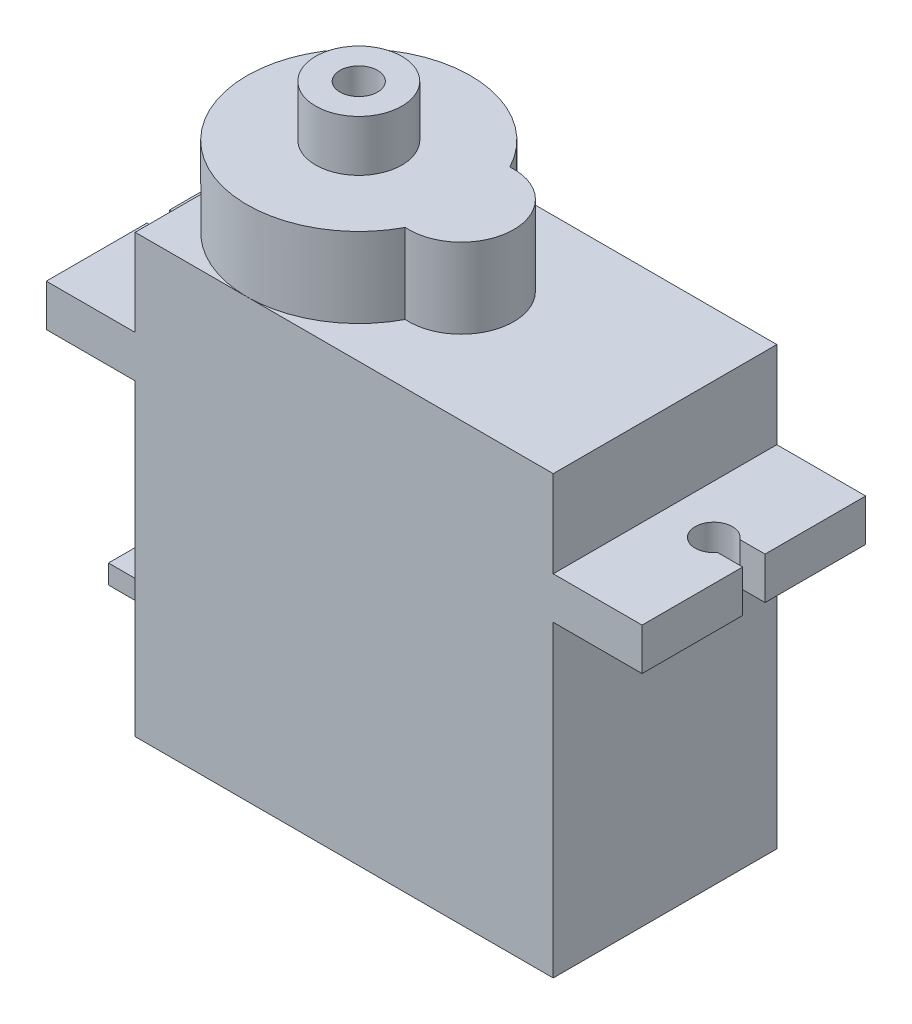
SolidWorks part; units mm, degrees
ref_plane "Front Plane" through (0, 0, 0) normal (0, 0, 1) x (1, 0, 0)
ref_plane "Top Plane" through (0, 0, 0) normal (0, 1, 0) x (1, 0, 0)
ref_plane "Right Plane" through (0, 0, 0) normal (1, 0, 0) x (0, 0, -1)
sketch "Sketch1" plane through (0, 0, 0) normal (0, 1, 0) x (1, 0, 0)
  line L1 (0, 0) -> (22.7711, 0)
  line L2 (0, 0) -> (0, 12.18)
  line L3 (0, 12.18) -> (22.7711, 12.18)
  line L4 (22.7711, 0) -> (22.7711, 12.18)
  dimension "D1" = 12.18
  dimension "D2" = 22.7711
extrude "Boss-Extrude1" add sketch "Sketch1" along normal blind 23.79
ref_plane "Plane1" through (0, 19.0656, 0) normal (0, 1, 0) x (1, 0, 0)
sketch "Sketch3" plane through (0, 19.0656, 0) normal (0, 1, 0) x (1, 0, 0)
  line L0 (22.7711, 12.18) -> (0, 12.18) construction
  line L1 (-4.8387, 0) -> (27.6098, 0)
  line L2 (-4.8387, 0) -> (-4.8387, 12.18)
  line L3 (-4.8387, 12.18) -> (27.6098, 12.18)
  line L4 (27.6098, 0) -> (27.6098, 12.18)
  line L5 (0, 0) -> (22.7711, 0) construction
  point P6 (11.3856, 0)
  point P9 (11.3856, 0)
  dimension "D1" = 32.4485
extrude "Boss-Extrude2" add sketch "Sketch3" against normal blind 2.286
sketch "Sketch4" plane through (0, 19.0656, 0) normal (0, 1, 0) x (1, 0, 0)
  line L0 (-3.4671, 6.6996) -> (-3.4671, 5.4804) construction
  line L1 (-4.8387, 6.6996) -> (-3.4671, 6.6996)
  line L2 (-4.8387, 12.18) -> (-4.8387, 0) construction
  line L3 (-3.4671, 5.4804) -> (-4.8387, 5.4804)
  line L4 (-1.6383, 6.09) -> (-1.6383, 8.3545) construction
  line L5 (11.3856, 12.18) -> (11.3856, 0) construction
  line L6 (22.7711, 12.18) -> (0, 12.18) construction
  line L7 (0, 0) -> (22.7711, 0) construction
  line L8 (24.4094, 6.09) -> (24.4094, 8.3545) construction
  line L9 (26.2382, 6.6996) -> (26.2382, 5.4804) construction
  line L10 (26.2382, 5.4804) -> (27.6098, 5.4804)
  line L11 (27.6098, 6.6996) -> (26.2382, 6.6996)
  line L12 (-4.8387, 6.6996) -> (-4.8387, 5.4804)
  line L13 (27.6098, 6.6996) -> (27.6098, 5.4804)
  arc A0 (-3.4671, 6.6996) -> (-3.4671, 5.4804) centre (-2.6543, 6.09) cw
  arc A1 (26.2382, 6.6996) -> (26.2382, 5.4804) centre (25.4254, 6.09) ccw
  point P6 (-3.4671, 6.09)
  point P8 (-4.8387, 6.09)
  dimension "D1" = 1.016
  dimension "D2" = 3.2004
  dimension "D3" = 1.2192
extrude "Cut-Extrude1" cut sketch "Sketch4" against normal through all
sketch "Sketch5" plane through (0, 23.79, 0) normal (0, 1, 0) x (1, 0, 0)
  line L0 (22.7711, 12.18) -> (0, 12.18) construction
  line L1 (0, 12.18) -> (0, 0) construction
  line L2 (0, 0) -> (22.7711, 0) construction
  line L3 (14.5288, 6.09) -> (14.5288, 9.2952) construction
  arc A0 (11.4717, 8.9405) -> (11.4717, 3.2395) centre (6.09, 6.09) ccw
  arc A1 (11.4717, 3.2395) -> (11.4717, 8.9405) centre (11.6713, 6.09) ccw
  dimension "D1" = 14.5288
  dimension "D2" = 5.715
extrude "Boss-Extrude3" add sketch "Sketch5" along normal blind 4.3434
sketch "Sketch6" plane through (0, 28.1334, 0) normal (0, 1, 0) x (1, 0, 0)
  circle A0 centre (6.09, 6.09) radius 2.3495
  arc A1 (11.4717, 8.9405) -> (11.4717, 3.2395) centre (6.09, 6.09) ccw construction
  dimension "D1" = 4.699
extrude "Boss-Extrude4" add sketch "Sketch6" along normal blind 2.7813 contours A0
sketch "Sketch7" plane through (0, 0, 0) normal (-1, 0, 0) x (0, 0, 1)
  line L0 (-12.18, 0) -> (0, 0) construction
  line L1 (-7.5378, 1.78) -> (-4.6422, 1.78)
  line L2 (-7.5378, 1.78) -> (-7.5378, 2.8214)
  line L3 (-7.5378, 2.8214) -> (-4.6422, 2.8214)
  line L4 (-4.6422, 1.78) -> (-4.6422, 2.8214)
  point P4 (-6.09, 1.78)
  point P7 (-6.09, 0)
  dimension "D1" = 1.0414
  dimension "D2" = 2.8956
  dimension "D3" = 1.78
extrude "Boss-Extrude5" add sketch "Sketch7" along normal blind 6.096
ref_axis "Axis1" through (6.09, 30.9147, -6.09) along (0, -1, 0)
ref_plane "Plane2" through (6.09, 0, 0) normal (-1, 0, 0) x (0, 0, 1)
sketch "Sketch8" plane through (0, 28.1334, 0) normal (0, 1, 0) x (1, 0, 0)
  circle A0 centre (6.09, 6.09) radius 3.556
  dimension "D1" = 7.112
extrude "Boss-Extrude6" [suppressed] add sketch "Sketch8" along normal blind 4.4577
sketch "Sketch9" [suppressed] plane through (0, 31.9532, 0) normal (0, 1, 0) x (1, 0, 0)
  line L0 (2.5019, 6.0579) -> (3.8735, 18.5674)
  line L1 (3.8735, 18.5674) -> (8.2423, 18.5674)
  line L2 (8.2423, 18.5674) -> (9.6139, 6.0579)
  line L3 (6.0579, 6.0579) -> (6.0579, 18.5674) construction
  line L4 (2.5019, 6.0579) -> (9.6139, 6.0579)
  line L5 (8.9281, 12.3127) -> (6.0579, 12.3127) construction
  line L6 (6.0579, 12.3127) -> (3.1877, 12.3127) construction
  circle A0 centre (6.0579, 6.0579) radius 3.556 construction
  point P10 (6.0579, 18.5674)
  point P18 (6.0579, 2.5019)
  dimension "D1" = 4.3688
  dimension "D2" = 16.0655
extrude "Boss-Extrude7" [suppressed] add sketch "Sketch9" against normal blind 1.651
sketch "Sketch11" [suppressed] plane through (0, 31.9532, 0) normal (0, 1, 0) x (1, 0, 0)
  circle A0 centre (6.0579, 6.0579) radius 2.4257
  arc A1 (2.5864, 6.8284) -> (9.5294, 6.8284) centre (6.0579, 6.0579) ccw construction
  dimension "D1" = 4.8514
extrude "Cut-Extrude2" [suppressed] cut sketch "Sketch11" against normal blind 2.54
sketch "Sketch12" [suppressed] plane through (0, 29.4132, 0) normal (0, 1, 0) x (1, 0, 0)
  circle A0 centre (6.0579, 6.0579) radius 1.2001
  dimension "D1" = 2.4003
extrude "Cut-Extrude3" [suppressed] cut sketch "Sketch12" against normal up to surface (1.9177 mm away)
hole_wizard "M2.5x0.45 Tapped Hole1" positions "Sketch14" profile "Sketch15" tap size "M2.5x0.45" standard "ANSI Metric"
sketch "Sketch14" plane through (0, 30.9147, 0) normal (0, 1, 0) x (1, 0, 0)
  point P0 (6.09, 6.09)
sketch "Sketch15" plane through (6.09, 30.9147, -6.09) normal (1, 0, 0) x (0, 0, 1)
  line L0 (0, 0) -> (0, 4.6159)
  line L1 (0, 4.6159) -> (1.025, 4)
  line L2 (1.025, 4) -> (1.025, 0)
  line L5 (1.025, 0) -> (0, 0)
  line L10 (0, 4.6159) -> (-1.025, 4) construction
  line L11 (0, -6.35) -> (0, 107.95) construction
  dimension "Tap Drill Dia." = 2.05
  dimension "Tap Drill Depth" = 4
  dimension "Drill Angle" = 118
cosmetic thread "Hole Thread1" parameters "D1"=4, "D2"=2.5
ref_plane "Plane3" through (0, 26.2988, 0) normal (0, 1, 0) x (1, 0, 0)
